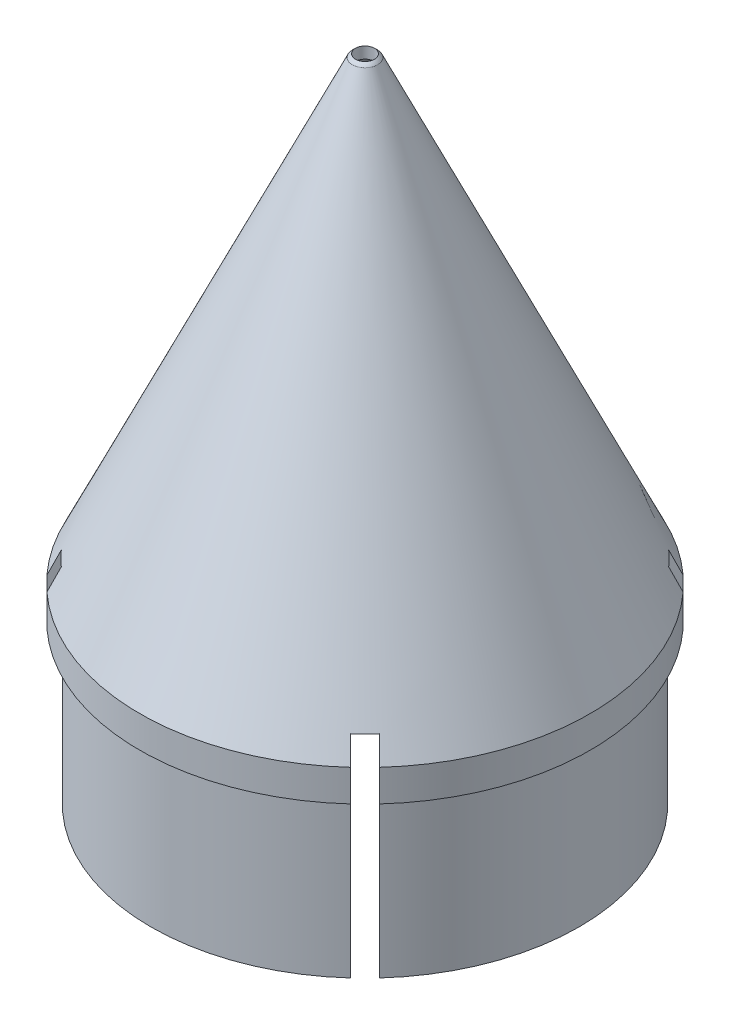
SolidWorks part; units mm, degrees
ref_plane "Front Plane" through (0, 0, 0) normal (0, 0, 1) x (1, 0, 0)
ref_plane "Top Plane" through (0, 0, 0) normal (0, 1, 0) x (1, 0, 0)
ref_plane "Right Plane" through (0, 0, 0) normal (1, 0, 0) x (0, 0, -1)
sketch "Sketch3" plane through (0, 0, 0) normal (0, 0, 1) x (1, 0, 0)
  line L1 (0, 0) -> (0, 155.682)
  line L4 (0, 0) -> (0, -50)
  line L5 (0, -50) -> (67.5, -50)
  line L6 (67.5, -50) -> (67.5, 0)
  line L9 (71, 0) -> (71, 10)
  line L11 (67.5, 0) -> (71, 0)
  line L12 (4, 153.682) -> (71, 10)
  line L13 (0, 229.1763) -> (0, 65.794) construction
  arc A0 (0, 155.682) -> (4, 153.682) centre (0, 150.682) cw
  point P11 (67.5, -50)
  point P14 (71, 10)
  dimension "Round yDim" = 2
  dimension "Lip Height" = 10
  dimension "Shoulder Height" = 50
  dimension "Half Angle" = 25
  dimension "Shoulder Diam" = 135
  dimension "Outer Diam" = 142
  dimension "Round xDim" = 8
revolve "Revolve1" add sketch "Sketch3" angle 360 about L1
shell "Shell1" thickness 2 removed face at (0, -50, -67.5)
sketch "Sketch7" plane through (0, 0, 0) normal (0, 1, 0) x (1, 0, 0)
  circle A0 centre (0, 0) radius 3
  dimension "D1" = 6
extrude "Cut-Extrude3" cut sketch "Sketch7" along normal through all
ref_plane "Plane1" through (0, 0, 0) normal (1, 0, 0) x (0, 0, -1)
sketch "Sketch8" plane through (0, 0, 0) normal (1, 0, 0) x (0, 0, -1)
  line L0 (-39.807, 40.9099) -> (-39.807, 20) construction
  line L1 (-44.807, 44.0901) -> (-44.807, 39.0901) construction
  line L2 (-44.807, 39.0901) -> (-39.807, 40.9099) construction
  line L3 (-39.807, 40.9099) -> (-39.807, 35.9099)
  line L4 (-44.807, 44.0901) -> (-44.807, 39.0901)
  line L5 (-44.807, 39.0901) -> (-39.807, 40.9099)
  line L6 (-39.807, 35.9099) -> (-44.807, 34.0901)
  line L7 (-44.807, 34.0901) -> (-57.5599, 34.0901)
  line L8 (-3, 151.0941) -> (-69, 9.5566) construction
  line L9 (-57.5599, 34.0901) -> (-44.807, 61.4387)
  line L10 (-44.807, 61.4387) -> (-44.807, 44.0901)
  dimension "D1" = 5
extrude "Boss-Extrude1" add sketch "Sketch8" along normal mid plane 15
sketch "Sketch9" plane through (0, 0, 0) normal (1, 0, 0) x (0, 0, -1)
  line L0 (-44.807, 39.0901) -> (-44.807, 60.1019) construction
  line L1 (-39.807, 40.9099) -> (-44.807, 39.0901) construction
  line L2 (-39.807, 35.9099) -> (-39.807, 40.9099) construction
  line L3 (-44.807, 34.0901) -> (-39.807, 35.9099) construction
  line L5 (-44.807, 39.0901) -> (-44.807, 60.1019)
  line L6 (-39.807, 40.9099) -> (-44.807, 39.0901)
  line L7 (-39.807, 35.9099) -> (-39.807, 40.9099)
  line L8 (-44.807, 34.0901) -> (-39.807, 35.9099)
  line L9 (-57.1133, 26.985) -> (-44.807, 34.0901)
  line L10 (-44.807, 34.0901) -> (-44.807, 39.0901) construction
  line L11 (-44.807, 60.1019) -> (-57.1133, 26.985)
  dimension "D1" = 120
extrude "Cut-Extrude4" cut sketch "Sketch9" against normal mid plane 3.5
pattern_circular "CirPattern1" count 2 over 360 about axis through (0, 0, 0) along (0, -1, 0) of "Boss-Extrude1", "Cut-Extrude4"
ref_axis "Axis1" through (0, 0, 0) along (0, -1, 0)
ref_plane "Plane2" through (0, 0, 0) normal (0.7071, 0, 0.7071) x (0, -1, 0)
sketch "Sketch11" plane through (0, 0, 0) normal (0.7071, 0, 0.7071) x (0, -1, 0)
  line L0 (-12.948, 58.5622) -> (-15.948, 63.7583) construction
  line L1 (-15.948, 63.7583) -> (1.3726, 73.7583) construction
  line L2 (1.3726, 73.7583) -> (4.3726, 68.5622) construction
  line L3 (4.3726, 68.5622) -> (-12.948, 58.5622) construction
  line L4 (-14.448, 61.1603) -> (2.8726, 71.1603) construction
  line L5 (-9.448, 65.5) -> (-2, 65.5) construction
  line L6 (-16.8959, 52.5) -> (-16.8959, 65.5776)
  line L7 (-16.8959, 65.5776) -> (-9.5566, 69)
  line L8 (-9.448, 52.5) -> (-14.942, 64.282) construction
  line L9 (-14.942, 64.282) -> (-15.7872, 66.0946) construction
  line L10 (-9.5566, 69) -> (-151.0941, 3) construction
  line L11 (-9.5566, 69) -> (-2, 69)
  line L15 (0, 0) -> (50, 0) construction
  line L16 (-2, 52.5) -> (-2, 65.5)
  line L17 (-2, 65.5) -> (-2, 69)
  circle A2 centre (-9.448, 52.5) radius 13 construction
  circle A3 centre (-9.448, 52.5) radius 10 construction
  arc A4 (-16.8959, 52.5) -> (-2, 52.5) centre (-9.448, 52.5) ccw
  point P6 (-14.448, 61.1603)
  dimension "D1" = 20
  dimension "D2" = 6
  dimension "D3" = 20
  dimension "D4" = 2
  dimension "LegAngle" = 30
extrude "Boss-Extrude3" add sketch "Sketch11" along normal mid plane 18
sketch "Sketch13" plane through (0, -50, 0) normal (0, -1, 0) x (1, 0, 0)
  line L0 (38.2206, -25.4926) -> (25.4926, -38.2206) construction
  line L1 (29.5585, -34.1547) -> (34.1547, -29.5585)
  line L2 (29.5585, -34.1547) -> (47.8539, -52.4501)
  line L3 (34.1547, -29.5585) -> (52.4501, -47.8539)
  arc A0 (47.8539, -52.4501) -> (52.4501, -47.8539) centre (0, 0) ccw
  circle A1 centre (0, 0) radius 71 construction
  point P11 (31.8566, -31.8566)
  point P12 (31.8566, -31.8566)
  dimension "D1" = 6.5
extrude "Cut-Extrude8" cut sketch "Sketch13" against normal up to surface (66.8959 mm away) up to face at (41.6371, 16.8959, -41.6371)
hole_wizard "M4 Clearance Hole1" positions "Sketch14" profile "Sketch15" hole size "M4" standard "ANSI Metric"
sketch "Sketch14" plane through (6.364, 0, 6.364) normal (0.7071, 0, 0.7071) x (0.7071, 0, -0.7071)
  arc A0 (52.5, 16.8959) -> (52.5, 2) centre (52.5, 9.448) ccw construction
  point P0 (52.5, 9.448)
sketch "Sketch15" plane through (43.4871, 9.448, -30.7591) normal (0, 1, 0) x (0.7071, 0, -0.7071)
  line L0 (0, 0) -> (0, 19.4421)
  line L1 (0, 19.4421) -> (2.4, 18)
  line L2 (2.4, 18) -> (2.4, 0)
  line L5 (2.4, 0) -> (0, 0)
  line L10 (0, 19.4421) -> (-2.4, 18) construction
  line L11 (0, -6.35) -> (0, 107.95) construction
  dimension "Hole Dia." = 4.8
  dimension "Hole Depth" = 18
  dimension "Drill Angle" = 118
pattern_circular "CirPattern4" count 4 over 360 about axis through (0, 0, 0) along (0, -1, 0) of "M4 Clearance Hole1", "Cut-Extrude8", "Boss-Extrude3"
equation "\"LegAngle\"=30"
